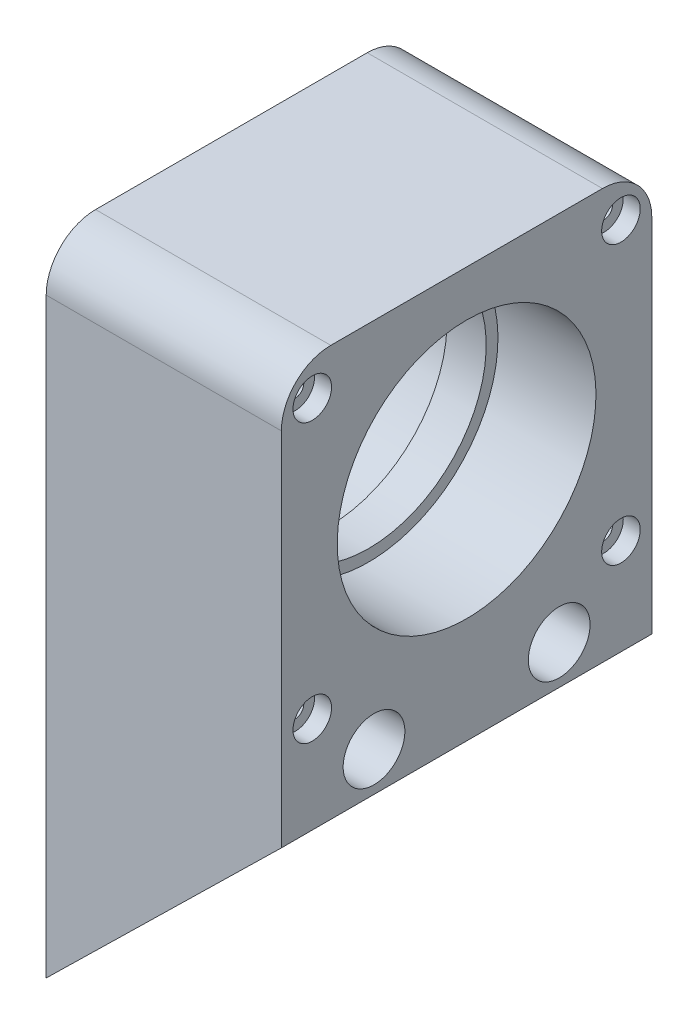
SolidWorks part; units mm, degrees
ref_plane "Front Plane" through (0, 0, 0) normal (0, 0, 1) x (1, 0, 0)
ref_plane "Top Plane" through (0, 0, 0) normal (0, 1, 0) x (1, 0, 0)
ref_plane "Right Plane" through (0, 0, 0) normal (1, 0, 0) x (0, 0, -1)
sketch "Sketch1" plane through (0, 0, 0) normal (0, 0, 1) x (1, 0, 0)
  line L0 (381, 457.2) -> (457.2, 457.2)
  line L1 (457.2, 457.2) -> (457.2, 431.8)
  line L2 (381, 457.2) -> (381, 357.2)
  line L5 (381, 357.2) -> (457.2, 431.8)
  dimension "D1" = 76.2
  dimension "D2" = 100
extrude "Boss-Extrude1" add sketch "Sketch1" along normal blind 120
sketch "Sketch3" plane through (457.2, 0, 0) normal (1, 0, 0) x (0, 0, -1)
  line L1 (-120, 431.8) -> (0, 431.8)
  line L2 (-120, 431.8) -> (-120, 357.2)
  line L3 (-120, 357.2) -> (0, 357.2)
  line L4 (0, 431.8) -> (0, 357.2)
  circle A0 centre (-90, 394.5) radius 4.25
  circle A1 centre (-30, 394.5) radius 4.25
  circle A2 centre (-90, 444.5) radius 4.25
  circle A3 centre (-30, 444.5) radius 4.25
  dimension "D1" = 30
  dimension "D2" = 30
  dimension "D3" = 37.3
  dimension "D4" = 37.3
extrude "Cut-Extrude1" cut sketch "Sketch3" against normal blind 120 contours A1 | A0
sketch "Sketch5" plane through (457.2, 0, 0) normal (1, 0, 0) x (0, 0, -1)
  circle A0 centre (-90, 394.5) radius 10
  circle A1 centre (-30, 394.5) radius 10
  circle A2 centre (-90, 444.5) radius 10
  circle A3 centre (-30, 444.5) radius 10
extrude "Cut-Extrude2" cut sketch "Sketch5" against normal blind 53
sketch "Sketch6" plane through (457.2, 0, 0) normal (1, 0, 0) x (0, 0, -1)
  circle A0 centre (-90, 444.5) radius 4.25
  circle A1 centre (-30, 444.5) radius 4.25
extrude "Cut-Extrude3" cut sketch "Sketch6" against normal blind 103
sketch "Sketch7" plane through (0, 457.2, 0) normal (0, 1, 0) x (1, 0, 0)
  line L1 (381, 0) -> (457.2, 0)
  line L2 (381, 0) -> (381, -120)
  line L3 (381, -120) -> (457.2, -120)
  line L4 (457.2, 0) -> (457.2, -120)
extrude "Boss-Extrude2" add sketch "Sketch7" along normal blind 101.6
sketch "Sketch8" plane through (381, 0, 0) normal (-1, 0, 0) x (0, 0, 1)
  line L0 (120, 457.2) -> (0, 457.2)
  line L1 (120, 558.8) -> (120, 357.2) construction
  line L2 (0, 558.8) -> (0, 357.2) construction
  line L3 (0, 558.8) -> (120, 558.8) construction
  circle A0 centre (60, 508) radius 41.91
  dimension "D1" = 101.6
  dimension "D2" = 50.8
extrude "Cut-Extrude4" cut sketch "Sketch8" against normal blind 31.75 contours A0 region at (381, 508, 60)
sketch "Sketch9" plane through (457.2, 0, 0) normal (1, 0, 0) x (0, 0, -1)
  line L0 (-120, 558.8) -> (0, 558.8) construction
  circle A0 centre (-60, 508) radius 41.91
  dimension "D1" = 50.8
extrude "Cut-Extrude5" cut sketch "Sketch9" against normal blind 31.75
sketch "Sketch10" plane through (457.2, 0, 0) normal (1, 0, 0) x (0, 0, -1)
  circle A0 centre (-60, 508) radius 38.1
extrude "Cut-Extrude6" cut sketch "Sketch10" against normal blind 76.2
sketch "Sketch13" plane through (0, 558.8, 0) normal (0, 1, 0) x (1, 0, 0)
  line L1 (381, 0) -> (457.2, 0)
  line L2 (381, 0) -> (381, -120)
  line L3 (381, -120) -> (457.2, -120)
  line L4 (457.2, 0) -> (457.2, -120)
extrude "Boss-Extrude3" add sketch "Sketch13" along normal blind 6
sketch "Sketch11" plane through (457.2, 0, 0) normal (1, 0, 0) x (0, 0, -1)
  line L0 (-120, 431.8) -> (-120, 564.8) construction
  line L1 (-110, 553) -> (-10, 553)
  line L2 (-110, 553) -> (-110, 463)
  line L3 (-110, 463) -> (-10, 463)
  line L4 (-10, 553) -> (-10, 463)
  line L5 (0, 431.8) -> (0, 564.8) construction
  circle A0 centre (-60, 508) radius 5.3331
  circle A1 centre (-110, 553) radius 2.75
  circle A2 centre (-10, 553) radius 2.75
  circle A3 centre (-10, 463) radius 2.75
  circle A4 centre (-110, 463) radius 2.75
  dimension "D1" = 10
  dimension "D2" = 10
  dimension "D3" = 45
  dimension "D4" = 90
extrude "Cut-Extrude7" cut sketch "Sketch11" against normal blind 84.4 contours L1 A1 L2 | L2 A1 L1 | L4 A2 L1 | L1 A2 L4 | L3 A3 L4 | L4 A3 L3 | L2 A4 L3 | L3 A4 L2 region at (457.2, 553.389, 110.389) region at (457.2, 551.8329, 108.8329) region at (457.2, 553.389, 9.611) region at (457.2, 551.8329, 11.1671) region at (457.2, 464.1671, 108.8329) region at (457.2, 462.611, 110.389) region at (457.2, 462.611, 9.611) region at (457.2, 464.1671, 11.1671)
sketch "Sketch12" plane through (457.2, 0, 0) normal (1, 0, 0) x (0, 0, -1)
  circle A0 centre (-110, 553) radius 6.25
  circle A1 centre (-10, 553) radius 6.25
  circle A2 centre (-10, 463) radius 6.25
  circle A3 centre (-110, 463) radius 6.25
extrude "Cut-Extrude8" cut sketch "Sketch12" against normal blind 5.5
fillet "Fillet1" radius 16 2 edges at (419.1, 564.8, 0) (419.1, 564.8, 120)
